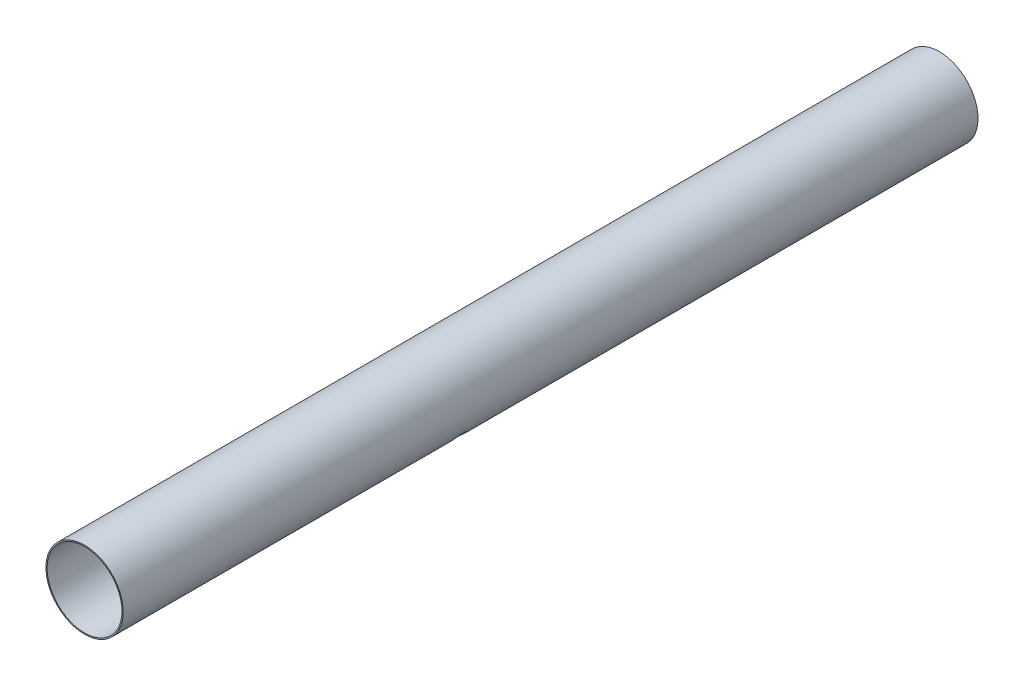
SolidWorks part; units mm, degrees
material "E-Glass Fiber"
ref_plane "Front" through (0, 0, 0) normal (0, 0, 1) x (1, 0, 0)
ref_plane "Top" through (0, 0, 0) normal (0, 1, 0) x (1, 0, 0)
ref_plane "Right" through (0, 0, 0) normal (1, 0, 0) x (0, 0, -1)
sketch "Sketch1" plane through (0, 0, 0) normal (0, 0, 1) x (1, 0, 0)
  circle A0 centre (0, 0) radius 78.6
  circle A1 centre (0, 0) radius 76.2
  dimension "D1" = 157.2
  dimension "D2" = 152.4
  dimension "D3" = 2.4
extrude "Boss-Extrude1" add sketch "Sketch1" along normal blind 1740
sketch "Sketch4" plane through (0, 0, 0) normal (0, 0, 1) x (1, 0, 0)
  line L0 (0, 0) -> (25.0476, -25.0476) construction
  line L1 (0, 0) -> (0, -24.8691) construction
  dimension "D1" = 45
ref_plane "Plane1" through (0, 0, 0) normal (0.7071, -0.7071, 0) x (0, 0, -1)
sketch "Sketch5" plane through (0, 0, 0) normal (0.7071, -0.7071, 0) x (0, 0, -1)
  line L0 (0, -78.6) -> (0, 78.6) construction
  circle A0 centre (-1034.89, 0) radius 15
  dimension "D1" = 30
  dimension "D2" = 1034.89
extrude "Cut-Extrude2" cut sketch "Sketch5" along normal through all
